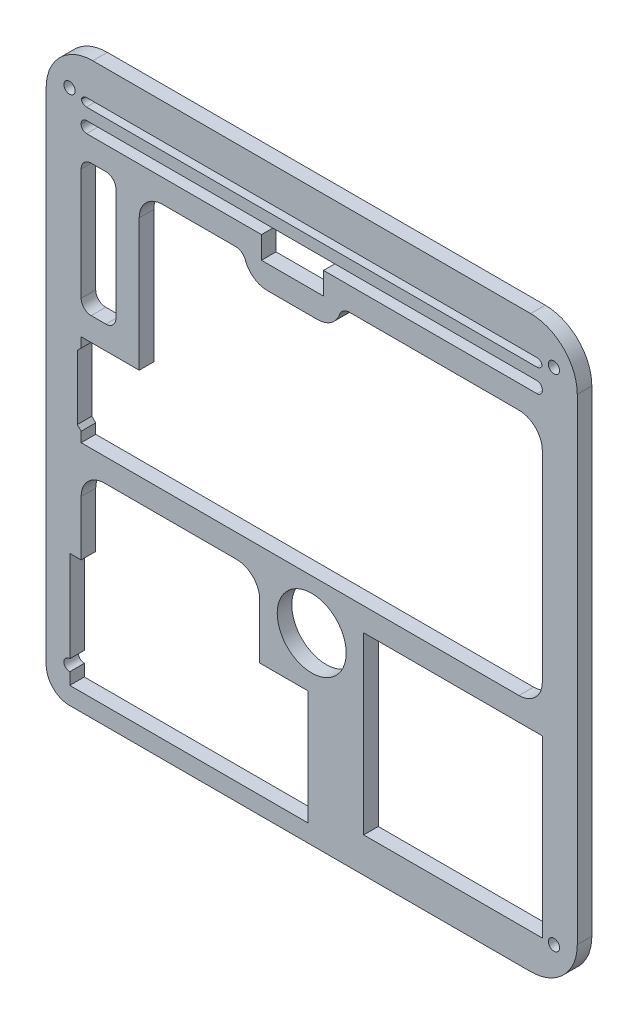
SolidWorks part; units mm, degrees
ref_plane "Front Plane" through (0, 0, 0) normal (0, 0, 1) x (1, 0, 0)
ref_plane "Top Plane" through (0, 0, 0) normal (0, 1, 0) x (1, 0, 0)
ref_plane "Right Plane" through (0, 0, 0) normal (1, 0, 0) x (0, 0, -1)
sketch "Sketch1" plane through (0, 0, 0) normal (0, 0, 1) x (1, 0, 0)
  line L0 (63.9883, 52.5442) -> (63.9883, 48.7342) construction
  line L1 (6.1648, -9.556) -> (64.0322, -9.556)
  line L2 (6.1648, -9.556) -> (6.1648, 52.5442)
  line L3 (6.1648, 52.5442) -> (64.0322, 52.5442)
  line L4 (64.0322, -9.556) -> (64.0322, 52.5442)
  line L5 (60.2222, 48.7342) -> (9.9748, 48.7342)
  line L6 (60.2222, 48.7342) -> (60.2222, -5.746)
  line L7 (60.2222, -5.746) -> (9.9748, -5.746)
  line L8 (9.9748, 48.7342) -> (9.9748, -5.746)
  line L9 (63.9883, 50.6392) -> (18.0707, 50.6392) construction
  line L10 (9.9748, 39.3805) -> (6.1648, 39.3805) construction
  line L11 (8.0698, 39.3805) -> (8.0698, 23.9527) construction
  line L12 (13.5248, -5.746) -> (13.5248, -9.556) construction
  line L13 (13.5248, -7.651) -> (21.1598, -7.651) construction
  line L14 (64.0322, 38.1916) -> (60.2222, 38.1916) construction
  line L15 (62.1272, 38.1916) -> (62.1272, 22.3321) construction
  line L16 (48.6748, 50.6392) -> (23.5288, 50.6392) construction
  line L17 (62.1272, 27.1202) -> (62.1272, 39.363) construction
  line L18 (8.0698, 15.868) -> (8.0698, 3.6252) construction
  line L19 (35.2238, -7.651) -> (34.6952, -7.651) construction
  dimension "D1" = 3.81
  dimension "D2" = 3.81
extrude "Boss-Extrude1" add sketch "Sketch1" along normal blind 1.5875
sketch "Sketch2" plane through (0, 0, 0) normal (0, 0, -1) x (-1, 0, 0)
  line L0 (-60.2222, -5.746) -> (-60.2222, 48.7342) construction
  line L1 (-60.2222, 15.868) -> (-9.9748, 15.868)
  line L2 (-60.2222, 15.868) -> (-60.2222, 13.328)
  line L3 (-60.2222, 13.328) -> (-9.9748, 13.328)
  line L4 (-9.9748, 15.868) -> (-9.9748, 13.328)
  line L5 (-9.9748, 48.7342) -> (-9.9748, -5.746) construction
  line L6 (-13.0532, 15.868) -> (-50.7532, 15.868) construction
  line L7 (-36.3812, 45.3306) -> (-36.3812, 43.2224) construction
  line L8 (-29.6248, 43.2224) -> (-29.6248, 45.3306) construction
  line L9 (-25.4592, 42.9049) -> (-46.8968, 42.9049) construction
  line L11 (-60.2222, 45.3306) -> (-36.3812, 45.3306)
  line L12 (-60.2222, 45.3306) -> (-60.2222, 42.7906)
  line L13 (-60.2222, 42.7906) -> (-38.2862, 42.7906)
  line L14 (-9.9748, 45.3306) -> (-9.9748, 42.7906)
  line L15 (-60.2222, 47.8325) -> (-9.9748, 47.8325)
  line L16 (-60.2222, 47.8325) -> (-60.2222, 46.5625)
  line L17 (-60.2222, 46.5625) -> (-9.9748, 46.5625)
  line L18 (-9.9748, 47.8325) -> (-9.9748, 46.5625)
  line L20 (-55.2788, 45.3306) -> (-16.9248, 45.3306) construction
  line L21 (-55.2788, 46.5625) -> (-16.9248, 46.5625) construction
  line L22 (-36.3812, 42.9049) -> (-36.3812, 45.3306)
  line L23 (-29.6248, 42.9049) -> (-36.3812, 42.9049)
  line L24 (-29.6248, 42.9049) -> (-29.6248, 45.3306)
  line L25 (-38.2862, 42.7906) -> (-38.2862, 40.3649)
  line L26 (-38.2862, 40.3649) -> (-27.7198, 40.3649)
  line L27 (-27.7198, 40.3649) -> (-27.7198, 42.7906)
  line L28 (-27.7198, 42.7906) -> (-9.9748, 42.7906)
  line L29 (-29.6248, 45.3306) -> (-9.9748, 45.3306)
  dimension "D1" = 2.54
  dimension "D2" = 1.905
  dimension "D3" = 2.54
  dimension "D4" = 1.905
  dimension "D5" = 1.27
extrude "Boss-Extrude2" add sketch "Sketch2" against normal up to surface (1.5875 mm away) up to face at (35.0985, 21.4941, 1.5875)
sketch "Sketch3" plane through (0, 0, 0) normal (0, 0, -1) x (-1, 0, 0)
  line L11 (-16.3032, 25.868) -> (-13.0532, 25.868) construction
  line L12 (-16.3032, 25.868) -> (-13.0532, 25.868)
  line L13 (-13.0532, 25.868) -> (-9.9748, 25.868)
  line L14 (-9.9748, 42.7906) -> (-9.9748, 15.868) construction
  line L15 (-9.9748, 25.868) -> (-9.9748, 28.408)
  line L16 (-9.9748, 28.408) -> (-13.7632, 28.408)
  line L17 (-13.7632, 28.408) -> (-13.7632, 42.7906)
  line L18 (-27.7198, 42.7906) -> (-9.9748, 42.7906) construction
  line L19 (-13.7632, 42.7906) -> (-16.3032, 42.7906)
  line L20 (-16.3032, 42.7906) -> (-16.3032, 25.868)
  line L21 (-16.3032, 25.868) -> (-16.2412, 25.8471)
  line M27 (-27.7198, 42.7906) -> (-9.9748, 42.7906)
  line M28 (-9.9748, 42.7906) -> (-9.9748, 15.868)
  dimension "D3" = 2.54
  dimension "D4" = 2.54
extrude "Boss-Extrude3" add sketch "Sketch3" against normal up to surface (1.5875 mm away) contours L20 L12 L13 L16 L17 M27 M28 region at (14.4544, 33.0139, 0) up to face at (35.0985, 48.2834, 1.5875)
sketch "Sketch4" plane through (0, 0, 0) normal (0, 0, -1) x (-1, 0, 0)
  line L0 (-60.2222, 13.328) -> (-9.9748, 13.328) construction
  line L1 (-40.7627, 13.328) -> (-29.4343, 13.328)
  line L2 (-40.7627, 13.328) -> (-40.7627, -5.746)
  line L3 (-40.7627, -5.746) -> (-29.4343, -5.746)
  line L4 (-29.4343, 13.328) -> (-29.4343, -5.746)
  line L5 (-9.9748, -5.746) -> (-60.2222, -5.746) construction
  line L6 (-38.8577, 10.4578) -> (-40.7627, 10.4578) construction
  line L7 (-31.3393, 10.4578) -> (-29.4343, 10.4578) construction
  circle A0 centre (-35.0985, 10.4578) radius 3.7592 construction
  dimension "D1" = 1.905
extrude "Boss-Extrude4" add sketch "Sketch4" against normal up to surface (1.5875 mm away) up to face at (11.869, 35.5993, 1.5875)
sketch "Sketch5" plane through (0, 0, 0) normal (0, 0, -1) x (-1, 0, 0)
  line L0 (-8.7364, 4.8077) -> (-34.6952, 4.8077) construction
  line L3 (-34.6952, -7.651) -> (-34.6952, 4.8077) construction
  line L4 (-8.7364, -7.651) -> (-34.6952, -7.651) construction
  line L5 (-8.7364, -7.651) -> (-8.7364, 4.8077) construction
  line L6 (-8.7364, 4.8077) -> (-34.6952, 4.8077)
  line L7 (-34.6952, -7.651) -> (-34.6952, 4.8077)
  line L8 (-8.7364, -7.651) -> (-34.6952, -7.651)
  line L9 (-8.7364, -7.651) -> (-8.7364, 4.8077)
  circle A0 centre (-35.0985, 10.4578) radius 3.7592 construction
  circle A1 centre (-35.0985, 10.4578) radius 3.7592
extrude "Cut-Extrude1" cut sketch "Sketch5" against normal up to surface (1.5875 mm away) up to face at (50.4924, 3.791, 1.5875)
fillet "Fillet1" radius 5.08 3 edges at (64.0322, -9.556, 0.7937) (6.1648, 52.5442, 0.7937) (64.0322, 52.5442, 0.7937)
fillet "Fillet2" radius 2.54 7 edges at (16.3032, 42.7906, 0.7937) (27.7198, 40.3649, 0.7937) (60.2222, 42.7906, 0.7937) (60.2222, 15.868, 0.7937) (9.9748, 13.328, 0.7937) (29.4343, 13.328, 0.7937) (38.2862, 40.3649, 0.7937)
fillet "Fillet3" radius 1.0922 6 edges at (9.9748, 28.408, 0.7937) (13.7632, 28.408, 0.7937) (9.9748, 42.7906, 0.7937) (13.7632, 42.7906, 0.7937) (27.7198, 42.7906, 0.7937) (38.2862, 42.7906, 0.7937)
fillet "Fillet4" radius 0.5842 8 edges at (9.9748, 45.3306, 0.7937) (9.9748, 47.8325, 0.7937) (9.9748, 48.7342, 0.7937) (9.9748, 46.5625, 0.7937) (60.2222, 47.8325, 0.7937) (60.2222, 48.7342, 0.7937) (60.2222, 46.5625, 0.7937) (60.2222, 45.3306, 0.7937)
fillet "Fillet5" radius 2.54 1 edges at (6.1648, -9.556, 0.7937)
sketch "Sketch6" plane through (0, 0, 0) normal (0, 0, -1) x (-1, 0, 0)
  line L0 (-9.5532, 24.368) -> (-9.5532, 17.368) construction
  line L1 (-9.5532, 24.368) -> (-9.5532, 17.368)
  line L2 (-11.0532, 25.868) -> (-9.5532, 24.368) construction
  line L3 (-11.0532, 25.868) -> (-9.5532, 24.368)
  line L4 (-11.0532, 25.868) -> (-11.0532, 15.868)
  line L6 (-13.0532, 17.368) -> (-13.0532, 15.868)
  line L7 (-13.0532, 15.868) -> (-11.0532, 15.868)
  line L8 (-11.0532, 15.868) -> (-9.5532, 17.368)
  line L9 (-9.5532, 17.368) -> (-13.0532, 17.368)
  line L12 (-11.0532, 15.868) -> (-9.5532, 17.368)
  circle A0 centre (-61.4922, 48.7342) radius 0.6096 construction
  circle A1 centre (-8.7048, 48.7342) radius 0.6096 construction
  circle A2 centre (-61.4922, -5.746) radius 0.6096 construction
  circle A3 centre (-8.7048, -5.746) radius 0.6096 construction
  circle A4 centre (-61.4922, 48.7342) radius 0.6096
  circle A5 centre (-8.7048, 48.7342) radius 0.6096
  circle A6 centre (-61.4922, -5.746) radius 0.6096
  circle A7 centre (-8.7048, -5.746) radius 0.6096
  dimension "D1" = 0
extrude "Cut-Extrude2" cut sketch "Sketch6" against normal up to surface (1.5875 mm away) up to face at (31.3393, 10.4578, 1.5875)
